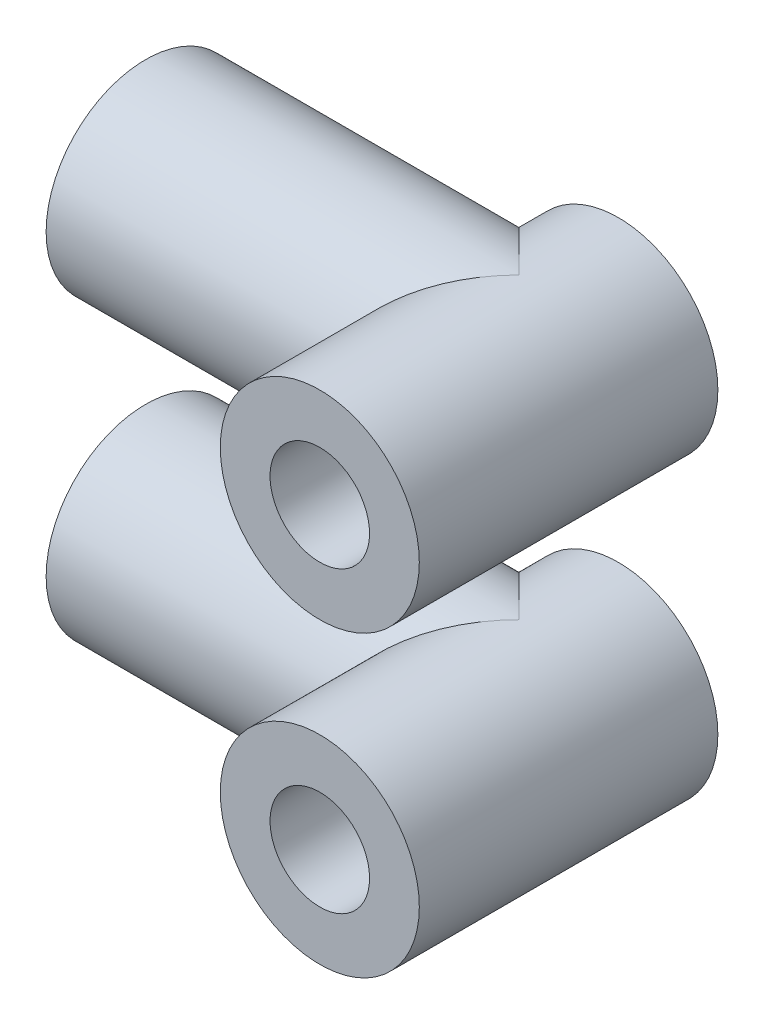
SolidWorks part; units mm, degrees
ref_plane "Front Plane" through (0, 0, 0) normal (0, 0, 1) x (1, 0, 0)
ref_plane "Top Plane" through (0, 0, 0) normal (0, 1, 0) x (1, 0, 0)
ref_plane "Right Plane" through (0, 0, 0) normal (1, 0, 0) x (0, 0, -1)
sketch "Sketch1" plane through (0, 0, 0) normal (0, 0, 1) x (1, 0, 0)
  circle A0 centre (0, 0) radius 2
  circle A1 centre (0, 0) radius 4
  dimension "D1" = 4
  dimension "D2" = 8
extrude "Boss-Extrude1" add sketch "Sketch1" along normal blind 12
sketch "Sketch2" plane through (0, 0, 0) normal (1, 0, 0) x (0, 0, -1)
  line L0 (0, -4) -> (0, 4) construction
  circle A0 centre (-4, 0) radius 2
  circle A1 centre (-4, 0) radius 4
  dimension "D1" = 4
  dimension "D2" = 8
  dimension "D3" = 4
extrude "Boss-Extrude2" add sketch "Sketch2" against normal blind 15
sketch "Sketch3" plane through (0, 0, 0) normal (0, 0, -1) x (-1, 0, 0)
  circle A0 centre (0, 0) radius 2
  circle A1 centre (0, 0) radius 2 construction
extrude "Cut-Extrude1" cut sketch "Sketch3" against normal through all
sketch "Sketch4" plane through (-15, 0, 0) normal (-1, 0, 0) x (0, 0, 1)
  circle A0 centre (4, 0) radius 2
  circle A1 centre (4, 0) radius 2 construction
extrude "Cut-Extrude2" cut sketch "Sketch4" against normal up to surface (15 mm away) up to plane "Right Plane"
ref_plane "Plane1" through (0, 6, 0) normal (0, 1, 0) x (1, 0, 0)
mirror "Mirror1" about plane through (0, 6, 0) normal (0, 1, 0) of bodies 104
